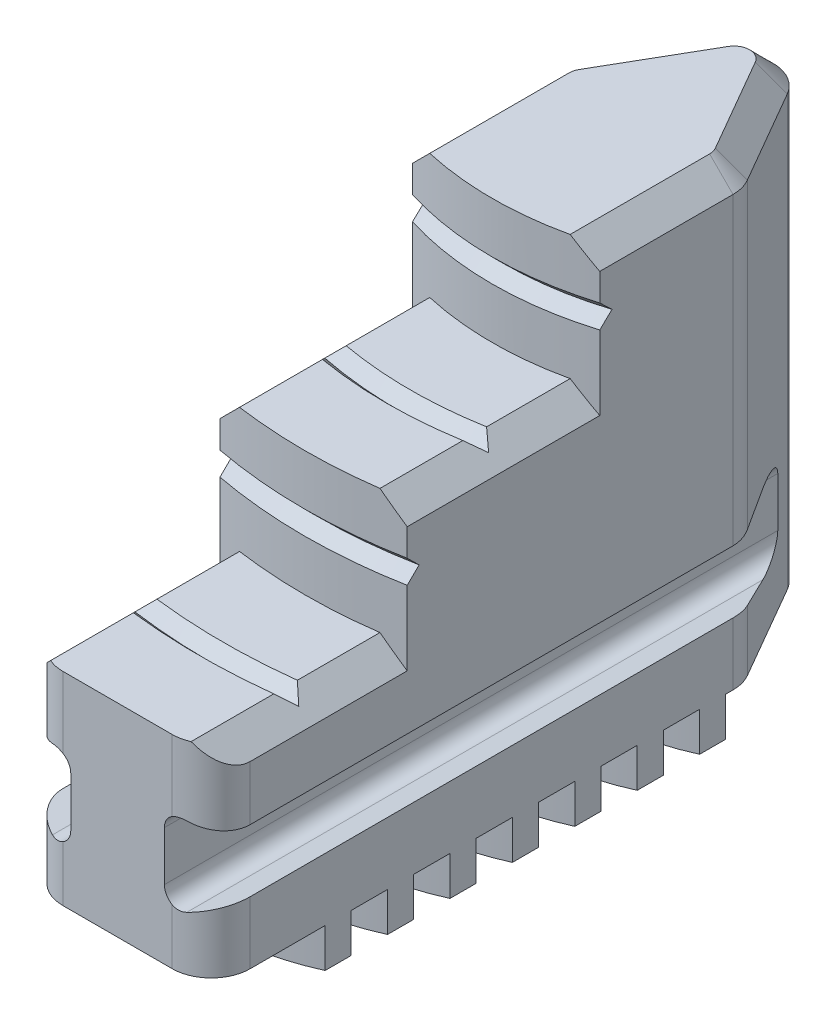
SolidWorks part; units mm, degrees
material "Alloy Steel"
ref_plane "Front Plane" through (0, 0, 0) normal (0, 0, 1) x (1, 0, 0)
ref_plane "Top Plane" through (0, 0, 0) normal (0, 1, 0) x (1, 0, 0)
ref_plane "Right Plane" through (0, 0, 0) normal (1, 0, 0) x (0, 0, -1)
sketch "Sketch1" plane through (0, 0, 0) normal (0, 1, 0) x (1, 0, 0)
  line L0 (-7, 0) -> (7, 0)
  line L1 (12, 5) -> (12, 66.8756)
  line L2 (11.3301, 69.3756) -> (4.3301, 81.5)
  line L3 (-4.3301, 81.5) -> (-11.3301, 69.3756)
  line L4 (-12, 66.8756) -> (-12, 5)
  arc A0 (7, 0) -> (12, 5) centre (7, 5) ccw
  arc A1 (12, 66.8756) -> (11.3301, 69.3756) centre (7, 66.8756) ccw
  arc A2 (4.3301, 81.5) -> (-4.3301, 81.5) centre (0, 79) ccw
  arc A3 (-11.3301, 69.3756) -> (-12, 66.8756) centre (-7, 66.8756) ccw
  arc A4 (-12, 5) -> (-7, 0) centre (-7, 5) ccw
  circle A5 centre (0, 89) radius 41 construction
  point P3 (0, 0)
  point P4 (0, 0)
  dimension "D1" = 5
  dimension "D3" = 82
  dimension "D5" = 84
  dimension "D2" = 30
  dimension "D4" = 89
  dimension "D6" = 24
extrude "Boss-Extrude1" add sketch "Sketch1" along normal blind 58
sketch "Sketch2" plane through (0, 0, 0) normal (1, 0, 0) x (0, 0, -1)
  line L0 (0, 26) -> (10.5, 26)
  line L1 (0, 26) -> (-2, 26)
  line L2 (10.5, 26) -> (12, 24.5)
  line L3 (12, 24.5) -> (13.5, 26)
  line L4 (13.5, 26) -> (24, 26)
  line L5 (24, 26) -> (24, 32.5)
  line L6 (24, 32.5) -> (25.5, 34)
  line L7 (25.5, 34) -> (24, 35.5)
  line L8 (24, 35.5) -> (24, 42)
  line L9 (24, 42) -> (34.5, 42)
  line L10 (34.5, 42) -> (36, 40.5)
  line L11 (36, 40.5) -> (37.5, 42)
  line L12 (37.5, 42) -> (48, 42)
  line L13 (48, 42) -> (48, 48.5)
  line L14 (48, 48.5) -> (49.5, 50)
  line L15 (49.5, 50) -> (48, 51.5)
  line L16 (48, 51.5) -> (48, 58)
  line L17 (5, 58) -> (66.8756, 58) construction
  line L20 (36, 62.1736) -> (36, 40.5) construction
  line L21 (49.5, 50) -> (-2, 50) construction
  line L22 (25.5, 34) -> (0.0892, 34) construction
  line L23 (12, 24.5) -> (12, 62) construction
  line L24 (89, 58) -> (89, 0) construction
  line L25 (-2, 26) -> (-2, 61)
  line L26 (-2, 61) -> (48, 61)
  line L27 (48, 61) -> (48, 58)
  line L28 (84, 0) -> (84, 58) construction
  point P2 (47.9108, 62.1736)
  point P30 (-2, 54.0691)
  dimension "D1" = 24
  dimension "D2" = 24
  dimension "D3" = 36
  dimension "D4" = 1.5
  dimension "D5" = 50
  dimension "D6" = 8
  dimension "D7" = 12
  dimension "D8" = 12
  dimension "D9" = 1.5
  dimension "D10" = 41
  dimension "D11" = 35
  dimension "D12" = 8
revolve "Cut-Revolve3" cut sketch "Sketch2" angle 360 about L24 region at (0, 46.1155, -19.4169)
sketch "Sketch3" plane through (0, 0, 0) normal (0, -1, 0) x (1, 0, 0)
  line L0 (-12, -54.5992) -> (-12, -57.9349)
  line L1 (12, -54.5992) -> (12, -57.9349)
  line L2 (0, -89) -> (-11.3301, -69.3756) construction
  line L3 (11.3301, -69.3756) -> (0, -89) construction
  line L4 (11.3301, -69.3756) -> (4.3301, -81.5) construction
  line L5 (-4.3301, -81.5) -> (-11.3301, -69.3756) construction
  line L6 (12, -5) -> (12, -66.8756) construction
  line L7 (-12, -66.8756) -> (-12, -5) construction
  line L8 (-12, -62.5992) -> (-12, -65.9349)
  line L9 (12, -62.5992) -> (12, -65.9349)
  line L10 (-12, -46.5992) -> (-12, -49.9349)
  line L11 (12, -46.5992) -> (12, -49.9349)
  line L12 (-12, -38.5992) -> (-12, -41.9349)
  line L13 (12, -38.5992) -> (12, -41.9349)
  line L14 (-12, -30.5992) -> (-12, -33.9349)
  line L15 (12, -30.5992) -> (12, -33.9349)
  line L16 (-12, -22.5992) -> (-12, -25.9349)
  line L17 (12, -22.5992) -> (12, -25.9349)
  line L18 (-12, -14.5992) -> (-12, -17.9349)
  line L19 (12, -14.5992) -> (12, -17.9349)
  line L22 (-12, -62.5992) -> (-12, -54.5992) construction
  line L23 (-12, -6.5992) -> (-12, -9.9349) [skipped]
  line L24 (12, -6.5992) -> (12, -9.9349) [skipped]
  arc A0 (12, -65.9349) -> (-12, -65.9349) centre (0, -89) ccw
  arc A1 (12, -62.5992) -> (-12, -62.5992) centre (0, -89) ccw
  arc A2 (12, -57.9349) -> (-12, -57.9349) centre (0, -81) ccw
  arc A3 (12, -54.5992) -> (-12, -54.5992) centre (0, -81) ccw
  arc A4 (12, -49.9349) -> (-12, -49.9349) centre (0, -73) ccw
  arc A5 (12, -46.5992) -> (-12, -46.5992) centre (0, -73) ccw
  arc A6 (12, -41.9349) -> (-12, -41.9349) centre (0, -65) ccw
  arc A7 (12, -38.5992) -> (-12, -38.5992) centre (0, -65) ccw
  arc A8 (12, -33.9349) -> (-12, -33.9349) centre (0, -57) ccw
  arc A9 (12, -30.5992) -> (-12, -30.5992) centre (0, -57) ccw
  arc A10 (12, -25.9349) -> (-12, -25.9349) centre (0, -49) ccw
  arc A11 (12, -22.5992) -> (-12, -22.5992) centre (0, -49) ccw
  arc A12 (12, -17.9349) -> (-12, -17.9349) centre (0, -41) ccw
  arc A13 (12, -14.5992) -> (-12, -14.5992) centre (0, -41) ccw
  arc A16 (12, -9.9349) -> (-12, -9.9349) centre (0, -33) ccw [skipped]
  arc A17 (12, -6.5992) -> (-12, -6.5992) centre (0, -33) ccw [skipped]
  dimension "D1" = 26
  dimension "D2" = 3
  dimension "D4" = 8
  dimension "D3" = 8
extrude "Boss-Extrude2" add sketch "Sketch3" along normal blind 5
sketch "Sketch4" plane through (0, 0, 0) normal (0, 0, 1) x (1, 0, 0)
  line L4 (12, 16) -> (8.6014, 17.0716)
  line L5 (12, 26) -> (12, 0) construction
  line L6 (6, 15.1641) -> (6, 8.8359)
  line L7 (8.6014, 6.9284) -> (12, 8)
  line L8 (12, 8) -> (12, 16)
  line L9 (7, 0) -> (12, 0) construction
  line L10 (0, 0) -> (0, 26) construction
  line L11 (-7, 0) -> (7, 0) construction
  line L12 (-7, 26) -> (7, 26) construction
  line L13 (-12, 8) -> (-12, 16)
  line L14 (-8.6014, 6.9284) -> (-12, 8)
  line L15 (-6, 15.1641) -> (-6, 8.8359)
  line L16 (-12, 16) -> (-8.6014, 17.0716)
  arc A2 (8.6014, 17.0716) -> (6, 15.1641) centre (8, 15.1641) ccw
  arc A3 (6, 8.8359) -> (8.6014, 6.9284) centre (8, 8.8359) ccw
  arc A4 (-6, 8.8359) -> (-8.6014, 6.9284) centre (-8, 8.8359) cw
  arc A5 (-8.6014, 17.0716) -> (-6, 15.1641) centre (-8, 15.1641) cw
  point P12 (-2.8741, 26)
  dimension "D3" = 2
  dimension "D1" = 8
  dimension "D2" = 8
  dimension "D4" = 35
  dimension "D5" = 6
extrude "Cut-Extrude1" cut sketch "Sketch4" against normal through all
chamfer "Chamfer1" distance 3 angle 45 11 edges at (-12, 26, -19.7885) (12, 26, -19.7885) (-12, 42, -44.3565) (12, 42, -44.3565) (-12, 58, -58.3355) (-11.8296, 58, -68.1697) (-7.8301, 58, -75.4378) (0, 58, -84) (7.8301, 58, -75.4378) (11.8296, 58, -68.1697) (12, 58, -58.3355)
